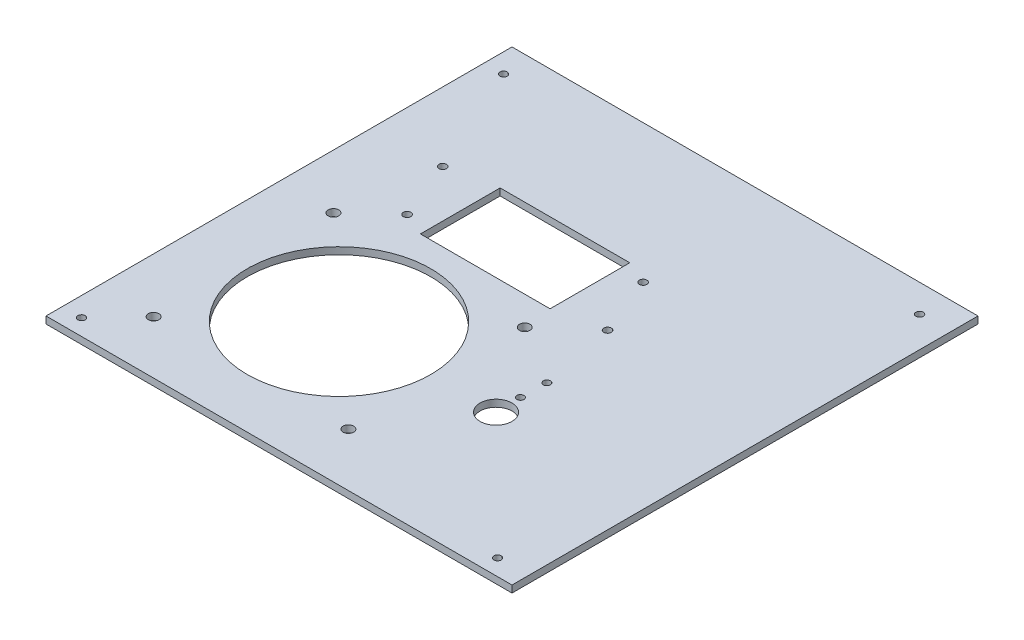
SolidWorks part; units mm, degrees
ref_plane "Front Plane" through (0, 0, 0) normal (0, 0, 1) x (1, 0, 0)
ref_plane "Top Plane" through (0, 0, 0) normal (0, 1, 0) x (1, 0, 0)
ref_plane "Right Plane" through (0, 0, 0) normal (1, 0, 0) x (0, 0, -1)
sketch "Sketch2" plane through (0, 0, 0) normal (0, 1, 0) x (1, 0, 0)
  line L1 (-114.3, 114.3) -> (114.3, 114.3)
  line L2 (-114.3, 114.3) -> (-114.3, -114.3)
  line L3 (-114.3, -114.3) -> (114.3, -114.3)
  line L4 (114.3, 114.3) -> (114.3, -114.3)
  line L5 (0, -114.3) -> (0, 114.3) construction
  line L6 (-114.3, 0) -> (114.3, 0) construction
  point P0 (0, 0)
  dimension "D1" = 228.6
  dimension "D2" = 228.6
extrude "Boss-Extrude2" add sketch "Sketch2" along normal blind 3.43
sketch "Sketch3" plane through (0, 3.43, 0) normal (0, 1, 0) x (1, 0, 0)
  circle A0 centre (-40.0396, -44.8231) radius 45
extrude "Cut-Extrude1" cut sketch "Sketch3" against normal blind 3.43
sketch "Sketch4" plane through (0, 3.43, 0) normal (0, 1, 0) x (1, 0, 0)
  circle A0 centre (-40.032, -44.8257) radius 57.88
  circle A1 centre (-40.032, -44.8257) radius 57.88
  circle A3 centre (7.9425, -88.2021) radius 2.6
  circle A4 centre (7.9425, -1.6923) radius 2.6
  circle A5 centre (-87.5818, 0) radius 2.6
  circle A6 centre (-87.5818, -88.2021) radius 2.6
  dimension "D1" = 5.2
  dimension "D2" = 5.2
  dimension "D3" = 5.2
  dimension "D4" = 5.2
  dimension "D5" = 115.76
extrude "Cut-Extrude2" cut sketch "Sketch4" against normal blind 3.43 contours A4
extrude "Cut-Extrude3" cut sketch "Sketch4<3>" against normal blind 3.43 contours A5
sketch "Sketch4<3>" plane through (0, 3.43, 0) normal (0, 1, 0) x (1, 0, 0) same geometry as "Sketch4"
extrude "Cut-Extrude4" cut sketch "Sketch4<4>" against normal blind 3.43 contours A6 | A3
sketch "Sketch4<4>" plane through (0, 3.43, 0) normal (0, 1, 0) x (1, 0, 0) same geometry as "Sketch4"
sketch "Sketch13" plane through (0, 3.43, 0) normal (0, 1, 0) x (1, 0, 0)
  line L0 (-57.3114, 51.4879) -> (-57.3114, 12.3879)
  line L2 (-57.3114, 12.3879) -> (6.2886, 12.3879)
  line L4 (6.2886, 51.4879) -> (-57.3114, 51.4879)
  line L6 (6.2886, 46.4779) -> (17.8386, 46.4779) construction
  line L7 (6.2886, 51.4879) -> (6.2886, 12.3879)
  line L8 (-57.3114, 17.3979) -> (-68.8614, 17.3979) construction
  line L10 (-57.3114, 46.4879) -> (-80.5114, 46.4879) construction
  line L12 (6.2886, 17.3879) -> (29.4886, 17.3879) construction
  dimension "D3" = 63.6
  dimension "D4" = 39.1
extrude "Cut-Extrude6" cut sketch "Sketch13" against normal blind 10
sketch "Sketch16" plane through (0, 3.43, 0) normal (0, 1, 0) x (1, 0, 0)
  circle A0 centre (99.2499, -106.3264) radius 1.8
  circle A1 centre (99.2499, 100.7058) radius 1.8
  circle A2 centre (-104.8408, 100.7058) radius 1.8
  circle A3 centre (-104.8408, -106.3264) radius 1.8
sketch "Sketch20" plane through (0, 3.43, 0) normal (0, 1, 0) x (1, 0, 0)
  line L0 (6.2886, 51.4879) -> (6.2886, 46.4879)
  line L1 (6.2886, 12.3879) -> (6.2886, 51.4879) construction
  line L2 (6.2886, 46.4879) -> (17.8386, 46.4879) construction
  line L3 (6.2886, 12.3879) -> (6.2886, 17.3879)
  line L4 (6.2886, 17.3879) -> (29.4886, 17.3879) construction
  line L5 (-57.3114, 51.4879) -> (-57.3114, 46.4879)
  line L6 (-57.3114, 51.4879) -> (-57.3114, 12.3879) construction
  line L7 (-57.3114, 46.4879) -> (-80.5114, 46.4879) construction
  line L8 (-57.3114, 12.3879) -> (-57.3114, 17.3879)
  line L9 (-57.3114, 17.3879) -> (-68.8614, 17.3879) construction
  dimension "D1" = 5
  dimension "D2" = 11.55
  dimension "D3" = 5
  dimension "D4" = 23.2
  dimension "D5" = 23.2
  dimension "D6" = 5
  dimension "D7" = 11.55
sketch "Sketch21" plane through (0, 3.43, 0) normal (0, 1, 0) x (1, 0, 0)
  circle A0 centre (-80.5114, 46.4879) radius 1.85
  circle A1 centre (-68.8614, 17.3879) radius 1.85
  circle A2 centre (29.4886, 17.3879) radius 1.85
  circle A3 centre (17.8386, 46.4879) radius 1.85
  dimension "D1" = 3.7
  dimension "D2" = 3.7
  dimension "D3" = 3.7
  dimension "D4" = 3.7
extrude "Cut-Extrude11" cut sketch "Sketch21" against normal blind 10
extrude "Cut-Extrude9" cut sketch "Sketch16" against normal blind 10
sketch "Sketch17" plane through (0, 3.43, 0) normal (0, 1, 0) x (1, 0, 0)
  circle A1 centre (36.9626, -19.8465) radius 1.73
  circle A2 centre (36.6769, -32.5433) radius 1.73
  circle A3 centre (36.9637, -44.7999) radius 7.8264
  point P0 (0, 0)
  point P11 (36.6604, -32.7735)
  point P12 (36.6769, -19.8465)
  dimension "D3" = 12.7
  dimension "D4" = 12.26
extrude "Cut-Extrude10" cut sketch "Sketch17" against normal blind 10
